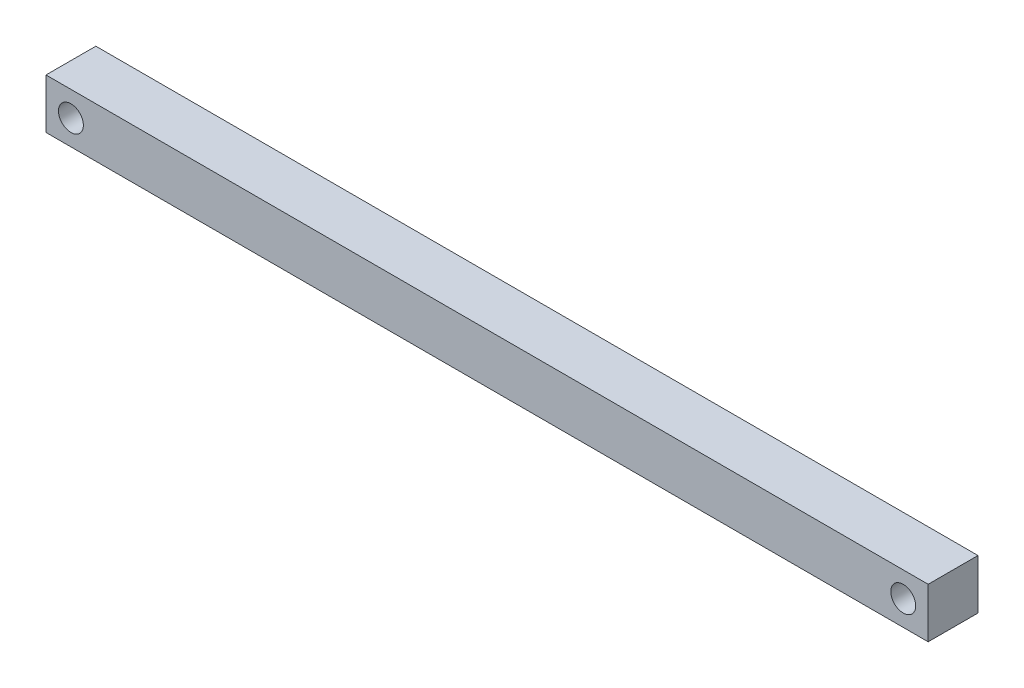
SolidWorks part; units mm, degrees
material "1060 Alloy for 162A"
ref_plane "Front Plane" through (0, 0, 0) normal (0, 0, 1) x (1, 0, 0)
ref_plane "Top Plane" through (0, 0, 0) normal (0, 1, 0) x (1, 0, 0)
ref_plane "Right Plane" through (0, 0, 0) normal (1, 0, 0) x (0, 0, -1)
sketch "Sketch1" plane through (0, 0, 0) normal (0, 0, 1) x (1, 0, 0)
  line L0 (250.5, 0) -> (-250.5, 0) construction
  line L1 (265.5, 15) -> (-265.5, 15)
  line L2 (265.5, 15) -> (265.5, -15)
  line L3 (265.5, -15) -> (-265.5, -15)
  line L4 (-265.5, 15) -> (-265.5, -15)
  line L5 (265.5, 15) -> (-265.5, -15) construction
  line L6 (265.5, -15) -> (-265.5, 15) construction
  circle A0 centre (-250.5, 0) radius 7.5
  circle A1 centre (250.5, 0) radius 7.5
  point P0 (0, 0)
  point P8 (0, 0)
  dimension "D2" = 15
  dimension "D1" = 30
  dimension "D3" = 501
  dimension "D4" = 15
extrude "Boss-Extrude1" add sketch "Sketch1" along normal mid plane 30
equation "\"A\"= 202"
equation "\"hole_diameter\"=15"
equation "\"D2@Sketch1\"=\"hole_diameter\""
equation "\"r5\"=501"
equation "\"D3@Sketch1\"=\"r5\""
equation "\"D4@Sketch1\"=\"hole_diameter\""
equation "\"r15\"=499"
